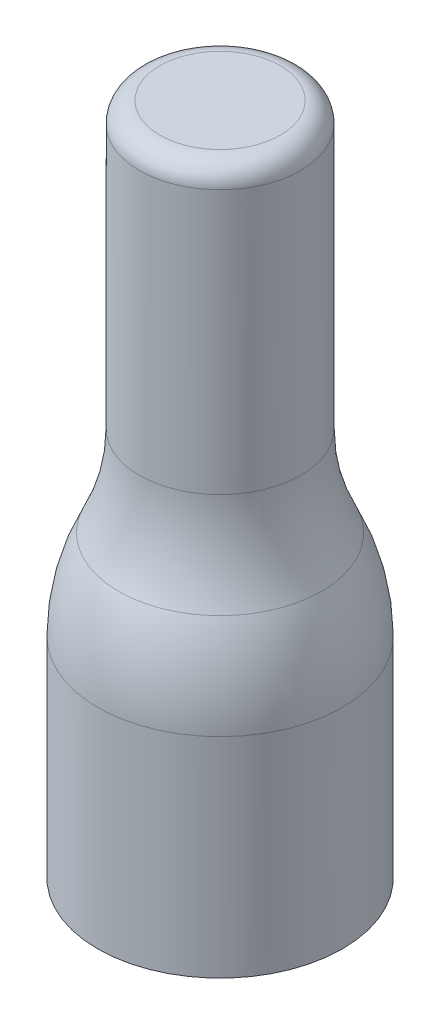
SolidWorks part; units mm, degrees
ref_plane "Front Plane" through (0, 0, 0) normal (0, 0, 1) x (1, 0, 0)
ref_plane "Top Plane" through (0, 0, 0) normal (0, 1, 0) x (1, 0, 0)
ref_plane "Right Plane" through (0, 0, 0) normal (1, 0, 0) x (0, 0, -1)
sketch "Sketch1" plane through (0, 0, 0) normal (0, 1, 0) x (1, 0, 0)
  circle A0 centre (0, 0) radius 4
  circle A1 centre (0, 0) radius 6
  dimension "D1" = 8
  dimension "D2" = 2
extrude "Boss-Extrude1" add sketch "Sketch1" along normal blind 10
sketch "Sketch2" plane through (0, 10, 0) normal (0, 1, 0) x (1, 0, 0)
  circle A0 centre (0, 0) radius 6
  circle A1 centre (0, 0) radius 6 construction
extrude "Boss-Extrude2" add sketch "Sketch2" along normal blind 3
sketch "Sketch3" plane through (0, 13, 0) normal (0, 1, 0) x (1, 0, 0)
  circle A0 centre (0, 0) radius 3.95
  dimension "D1" = 7.9
extrude "Boss-Extrude3" add sketch "Sketch3" along normal blind 20
fillet "Fillet1" radius 1 1 edges at (0, 33, 3.95)
fillet "Fillet2" radius 10 1 edges at (0, 13, 3.95)
fillet "Fillet3" radius 1 1 edges at (0, 0, 4)
fillet "Fillet4" radius 10 1 edges at (0, 13, 6)
